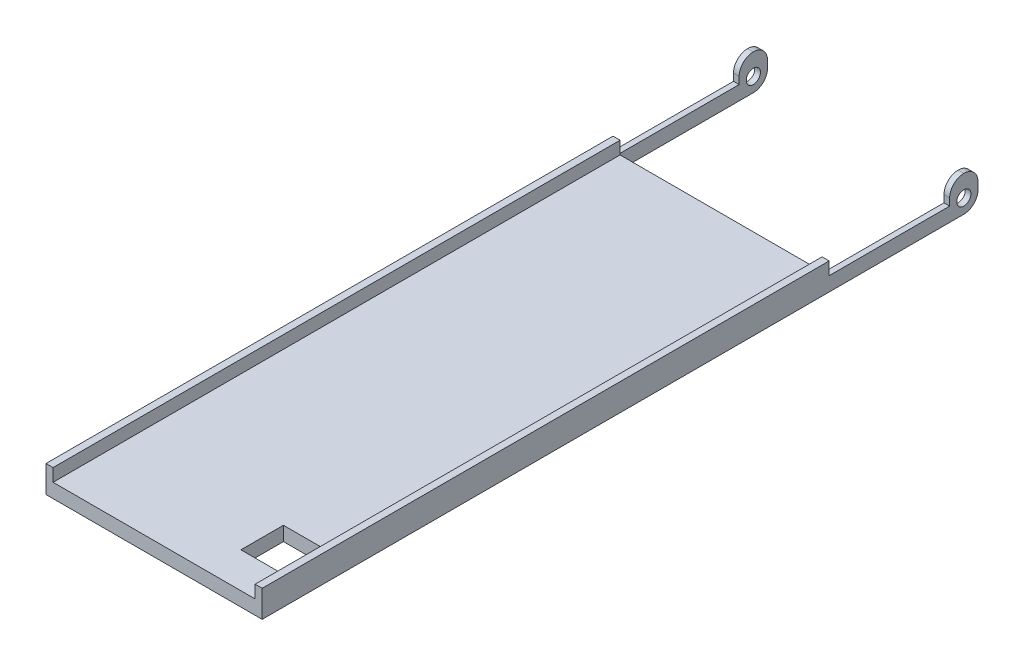
SolidWorks part; units mm, degrees
ref_plane "Front Plane" through (0, 0, 0) normal (0, 0, 1) x (1, 0, 0)
ref_plane "Top Plane" through (0, 0, 0) normal (0, 1, 0) x (1, 0, 0)
ref_plane "Right Plane" through (0, 0, 0) normal (1, 0, 0) x (0, 0, -1)
sketch "Sketch1" plane through (0, 0, 0) normal (0, 1, 0) x (1, 0, 0)
  line L1 (-15.25, -42.5) -> (15.25, -42.5)
  line L2 (-15.25, -42.5) -> (-15.25, 42.5)
  line L3 (-15.25, 42.5) -> (15.25, 42.5)
  line L4 (15.25, -42.5) -> (15.25, 42.5)
  line L5 (-15.25, -42.5) -> (15.25, 42.5) construction
  line L6 (-15.25, 42.5) -> (15.25, -42.5) construction
  point P0 (0, 0)
  dimension "D1" = 85
  dimension "D2" = 30.5
extrude "Boss-Extrude1" add sketch "Sketch1" along normal blind 2 contours L4 L3 L2 L1
sketch "Sketch2" plane through (0, 2, 0) normal (0, 1, 0) x (1, 0, 0)
  line L0 (0, 24.5) -> (0, -42.5) construction
  line L2 (-15.25, -42.5) -> (15.25, -42.5) construction
  line L3 (-15.25, -42.5) -> (-15.25, 42.5) construction
  line L4 (14.45, 42.5) -> (-14.45, 42.5)
  line L7 (-14.45, 42.5) -> (-14.45, 24.5)
  line L8 (14.45, 42.5) -> (14.45, 24.5)
  line L10 (-14.45, 24.5) -> (-14.45, 22.5)
  line L11 (-14.45, 22.5) -> (14.45, 22.5)
  line L12 (14.45, 24.5) -> (14.45, 22.5)
  dimension "D1" = 0.8
  dimension "D2" = 18
  dimension "D3" = 2
extrude "Cut-Extrude1" cut sketch "Sketch2" against normal up to vertex (2 mm away) up to point (15.25, 0, -42.5)
sketch "Sketch5" plane through (0, 2, 0) normal (0, 1, 0) x (1, 0, 0)
  line L0 (-15.25, -42.5) -> (-15.25, 42.5) construction
  line L1 (-14.45, 42.5) -> (-15.25, 42.5)
  line L2 (-14.45, 42.5) -> (-14.45, 38.5)
  line L3 (-14.45, 38.5) -> (-15.25, 38.5)
  line L4 (-15.25, 42.5) -> (-15.25, 38.5)
  dimension "D1" = 4
extrude "Boss-Extrude2" add sketch "Sketch5" along normal blind 3 contours L2 L3 L4 L1
sketch "Sketch6" plane through (-15.25, 0, 0) normal (-1, 0, 0) x (0, 0, 1)
  line L0 (42.5, 0) -> (-42.5, 0) construction
  line L1 (-42.5, 5) -> (-42.5, 0) construction
  circle A0 centre (-40.5, 2) radius 1
  dimension "D1" = 2
  dimension "D2" = 2
  dimension "D3" = 2
extrude "Cut-Extrude2" cut sketch "Sketch6" against normal up to vertex (0.8 mm away) contours A0 up to point (-14.45, 5, -42.5)
ref_plane "Plane1" through (0, 0, 0) normal (1, 0, 0) x (0, 0, -1)
mirror "Mirror1" about plane through (0, 0, 0) normal (1, 0, 0) of "Cut-Extrude2", "Boss-Extrude2"
fillet "Fillet1" radius 2 3 edges at (-14.85, 0, -42.5) (-14.85, 5, -42.5) (-14.85, 5, -38.5)
fillet "Fillet2" radius 2 3 edges at (14.85, 0, -42.5) (14.85, 5, -38.5) (14.85, 5, -42.5)
sketch "Sketch7" plane through (0, 0, 42.5) normal (0, 0, 1) x (1, 0, 0)
  line L1 (-15.25, 2) -> (15.25, 2)
  line L2 (-15.25, 2) -> (-15.25, 0)
  line L3 (-15.25, 0) -> (15.25, 0)
  line L4 (15.25, 2) -> (15.25, 0)
extrude "Boss-Extrude3" add sketch "Sketch7" along normal blind 16
sketch "Sketch8" plane through (0, 2, 0) normal (0, 1, 0) x (1, 0, 0)
  line L0 (-15.25, -58.5) -> (-15.25, 38.5) construction
  line L1 (15.25, -58.5) -> (-15.25, -58.5)
  line L2 (15.25, -58.5) -> (15.25, 21.5)
  line L3 (15.25, 21.5) -> (-15.25, 21.5)
  line L4 (-15.25, -58.5) -> (-15.25, 21.5)
  line L5 (-14.45, 22.5) -> (14.45, 22.5) construction
  dimension "D1" = 1
extrude "Boss-Extrude4" add sketch "Sketch8" along normal blind 1.8
sketch "Sketch9" plane through (0, 3.8, 0) normal (0, 1, 0) x (1, 0, 0)
  line L0 (15.25, 21.5) -> (-15.25, 21.5) construction
  line L1 (-14.25, 21.5) -> (14.25, 21.5)
  line L2 (-14.25, 21.5) -> (-14.25, -58.5)
  line L3 (-14.25, -58.5) -> (14.25, -58.5)
  line L4 (14.25, 21.5) -> (14.25, -58.5)
  line L5 (-15.25, -58.5) -> (15.25, -58.5) construction
  line L6 (-15.25, 21.5) -> (-15.25, -58.5) construction
  line L7 (15.25, -58.5) -> (15.25, 21.5) construction
  dimension "D1" = 1
  dimension "D2" = 1
extrude "Cut-Extrude3" cut sketch "Sketch9" against normal up to vertex (1.8 mm away) up to point (-14.45, 2, -22.5)
sketch "Sketch10" plane through (0, 0, -22.5) normal (0, 0, -1) x (-1, 0, 0)
  line L1 (-14.45, 2) -> (14.45, 2)
  line L2 (-14.45, 2) -> (-14.45, 0)
  line L3 (-14.45, 0) -> (14.45, 0)
  line L4 (14.45, 2) -> (14.45, 0)
extrude "Cut-Extrude4" cut sketch "Sketch10" against normal up to vertex (1 mm away) up to point (15.25, 2, -21.5)
sketch "Sketch11" plane through (0, 2, 0) normal (0, 1, 0) x (1, 0, 0)
  line L0 (14.25, -58.5) -> (14.25, 21.5) construction
  line L1 (14.25, -47.5) -> (7.25, -47.5)
  line L2 (14.25, -47.5) -> (14.25, -53.5)
  line L3 (14.25, -53.5) -> (7.25, -53.5)
  line L4 (7.25, -47.5) -> (7.25, -53.5)
  line L5 (-14.25, -58.5) -> (14.25, -58.5) construction
  dimension "D1" = 6
  dimension "D2" = 5
  dimension "D3" = 7
extrude "Cut-Extrude5" cut sketch "Sketch11" against normal up to vertex (2 mm away) up to point (15.25, 0, 58.5)
